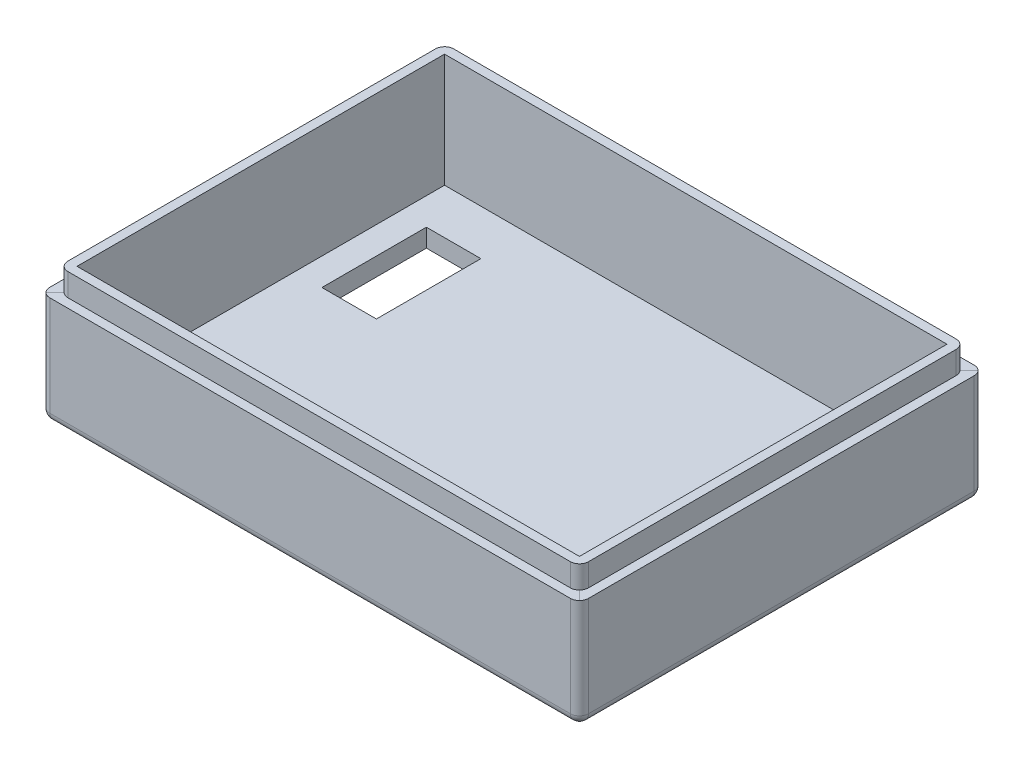
SolidWorks part; units mm, degrees
ref_plane "Front Plane" through (0, 0, 0) normal (0, 0, 1) x (1, 0, 0)
ref_plane "Top Plane" through (0, 0, 0) normal (0, 1, 0) x (1, 0, 0)
ref_plane "Right Plane" through (0, 0, 0) normal (1, 0, 0) x (0, 0, -1)
sketch "Sketch1" plane through (0, 0, 0) normal (0, 1, 0) x (1, 0, 0)
  line L1 (-29.655, 22.23) -> (29.655, 22.23)
  line L2 (-29.655, 22.23) -> (-29.655, -22.23)
  line L3 (-29.655, -22.23) -> (29.655, -22.23)
  line L4 (29.655, 22.23) -> (29.655, -22.23)
  dimension "D1" = 44.46
  dimension "D2" = 22.23
  dimension "D3" = 59.31
  dimension "D4" = 29.655
extrude "Boss-Extrude1" add sketch "Sketch1" along normal blind 2
sketch "Sketch2" plane through (0, 2, 0) normal (0, 1, 0) x (1, 0, 0)
  line L0 (27.655, -20.23) -> (27.655, 20.23)
  line L1 (27.655, 20.23) -> (-27.655, 20.23)
  line L2 (-27.655, 20.23) -> (-27.655, -20.23)
  line L3 (-27.655, -20.23) -> (27.655, -20.23)
  line L4 (-29.655, 22.23) -> (-29.655, -22.23)
  line L5 (-29.655, -22.23) -> (29.655, -22.23)
  line L6 (29.655, -22.23) -> (29.655, 22.23)
  line L7 (29.655, 22.23) -> (-29.655, 22.23)
  line L8 (-29.655, 22.23) -> (-29.655, -22.23)
  line L9 (-29.655, -22.23) -> (29.655, -22.23)
  line L10 (29.655, -22.23) -> (29.655, 22.23)
  line L11 (29.655, 22.23) -> (-29.655, 22.23)
  dimension "D1" = 0
  dimension "D2" = 2
extrude "Boss-Extrude2" add sketch "Sketch2" along normal blind 12.5
sketch "Sketch3" plane through (29.655, 0, 0) normal (1, 0, 0) x (0, 0, -1)
  line L1 (-21.23, 12) -> (-22.23, 12)
  line L2 (-21.23, 12) -> (-21.23, 14.5)
  line L3 (-21.23, 14.5) -> (-22.23, 14.5)
  line L4 (-22.23, 12) -> (-22.23, 14.5)
  dimension "D1" = 1
  dimension "D2" = 2.5
sketch "Sketch4" plane through (0, 14.5, 0) normal (0, 1, 0) x (1, 0, 0)
  line L0 (-29.655, -22.23) -> (29.655, -22.23) construction
  line L1 (-29.655, 22.23) -> (-29.655, -22.23) construction
  line L2 (29.655, 22.23) -> (-29.655, 22.23) construction
  line L3 (29.655, -22.23) -> (29.655, 22.23) construction
  line L4 (-29.655, -22.23) -> (29.655, -22.23)
  line L5 (-29.655, 22.23) -> (-29.655, -22.23)
  line L6 (29.655, 22.23) -> (-29.655, 22.23)
  line L7 (29.655, -22.23) -> (29.655, 22.23)
sweep "Cut-Sweep1" cut profiles "Sketch3" path "Sketch4"
fillet "Fillet1" radius 1 12 edges at (-29.655, 6, 22.23) (-29.655, 6, -22.23) (29.655, 6, -22.23) (-28.655, 13.25, -21.23) (28.655, 13.25, -21.23) (-28.655, 13.25, 21.23) (29.655, 0, 0) (0, 0, -22.23) (-29.655, 0, 0) (0, 0, 22.23)
sketch "Sketch5" plane through (0, 0, 0) normal (0, -1, 0) x (-1, 0, 0)
  line L0 (29.655, -21.23) -> (29.655, 21.23) construction
  line L1 (24.655, 3.73) -> (18.655, 3.73)
  line L2 (24.655, 3.73) -> (24.655, 15.23)
  line L3 (24.655, 15.23) -> (18.655, 15.23)
  line L4 (18.655, 3.73) -> (18.655, 15.23)
  line L5 (-27.655, 20.23) -> (27.655, 20.23) construction
  dimension "D1" = 11.5
  dimension "D2" = 6
  dimension "D3" = 5
  dimension "D4" = 5
extrude "Cut-Extrude1" cut sketch "Sketch5" against normal blind 10
sketch "Sketch6" plane through (0, 0, 0) normal (0, -1, 0) x (1, 0, 0)
  text T0 "A" font "Century Schoolbook" height in points 72
  point P4 (0, 0)
  dimension "D1" = 8
  dimension "D2" = 8
extrude "Boss-Extrude3" add sketch "Sketch6" along normal blind 2
